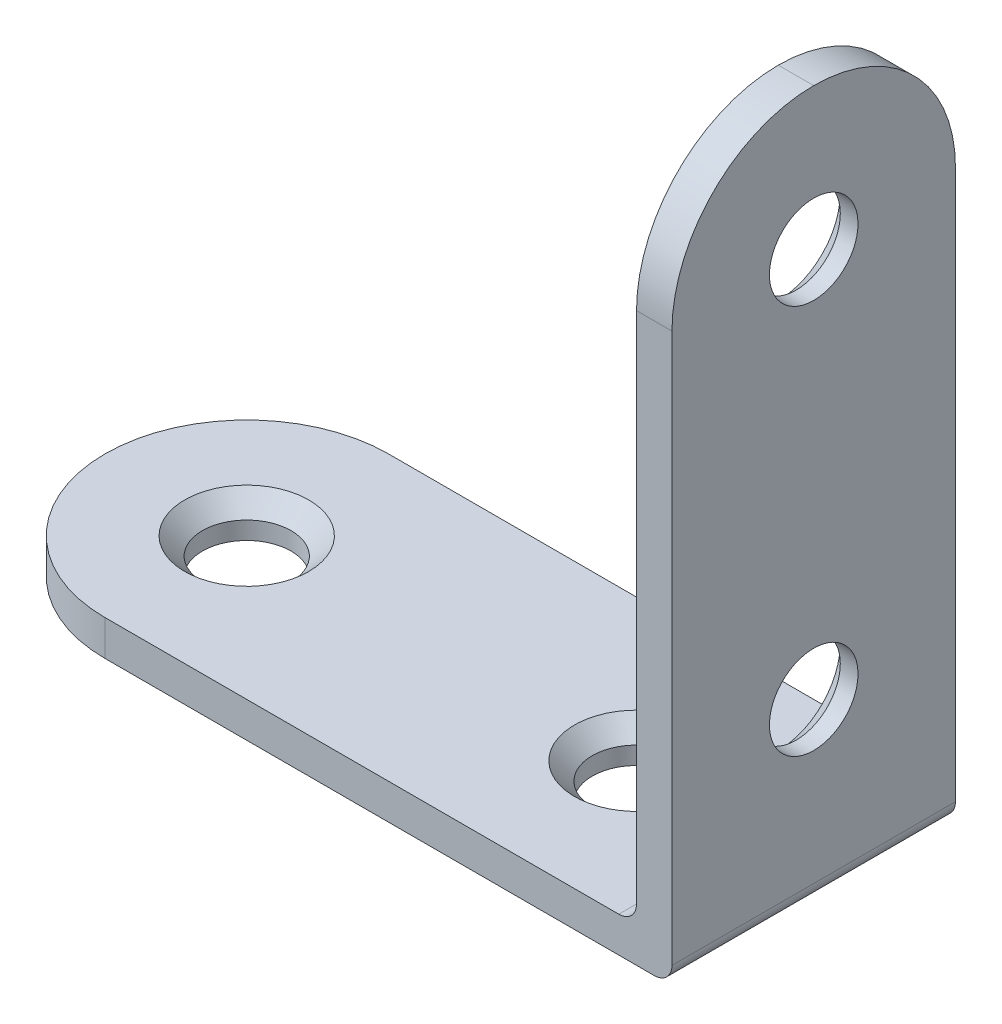
SolidWorks part; units mm, degrees
ref_plane "前视基准面" through (0, 0, 0) normal (0, 0, 1) x (1, 0, 0)
ref_plane "上视基准面" through (0, 0, 0) normal (0, 1, 0) x (1, 0, 0)
ref_plane "右视基准面" through (0, 0, 0) normal (1, 0, 0) x (0, 0, -1)
sketch "草图1" plane through (0, 0, 0) normal (0, 0, 1) x (1, 0, 0)
  line L0 (0, 38) -> (0, 0)
  line L1 (0, 0) -> (-38, 0)
  line L2 (-38, 0) -> (-38, -2)
  line L3 (-38, -2) -> (2, -2)
  line L4 (2, -2) -> (2, 38)
  line L5 (2, 38) -> (0, 38)
  dimension "D1" = 40
  dimension "D2" = 40
  dimension "D3" = 2
  dimension "D4" = 2
extrude "凸台-拉伸1" add sketch "草图1" along normal blind 16
fillet "圆角1" radius 8 4 edges at (-38, -1, 0) (-38, -1, 16) (1, 38, 16) (1, 38, 0)
sketch "草图2" plane through (0, 0, 0) normal (-1, 0, 0) x (0, 0, 1)
  circle A0 centre (8, 30) radius 2.5
  circle A1 centre (8, 8) radius 2.5
  dimension "D1" = 5
  dimension "D2" = 5
  dimension "D3" = 22
extrude "切除-拉伸1" cut sketch "草图2" against normal blind 16
sketch "草图3" plane through (0, 0, 0) normal (0, 1, 0) x (1, 0, 0)
  circle A0 centre (-30, -8) radius 2.5
  circle A1 centre (-8, -8) radius 2.5
  dimension "D1" = 5
  dimension "D2" = 5
  dimension "D3" = 22
extrude "切除-拉伸2" cut sketch "草图3" against normal blind 16
chamfer "倒角1" distance 1 angle 45 4 edges at (-32.5, 0, 8) (0, 27.5, 8) (0, 5.5, 8) (-10.5, 0, 8)
fillet "圆角2" radius 1 2 edges at (2, -2, 8) (0, 0, 8)
